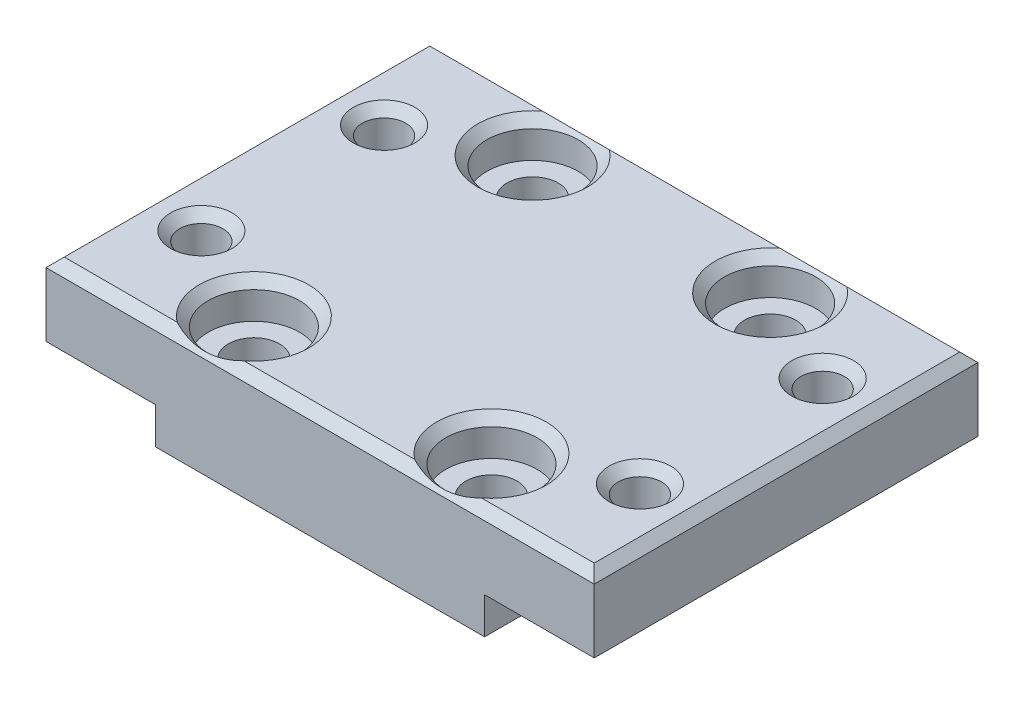
SolidWorks part; units mm, degrees
ref_plane "Plano frontal" through (0, 0, 0) normal (0, 0, 1) x (1, 0, 0)
ref_plane "Plano superior" through (0, 0, 0) normal (0, 1, 0) x (1, 0, 0)
ref_plane "Plano direito" through (0, 0, 0) normal (1, 0, 0) x (0, 0, -1)
sketch "Esboço1" plane through (0, 0, 0) normal (0, 1, 0) x (1, 0, 0)
  line L1 (-30, -21) -> (30, -21)
  line L2 (-30, -21) -> (-30, 21)
  line L3 (-30, 21) -> (30, 21)
  line L4 (30, -21) -> (30, 21)
  line L5 (-30, -21) -> (30, 21) construction
  line L6 (-30, 21) -> (30, -21) construction
  line L7 (-18, -21) -> (18, -21)
  line L8 (-18, -21) -> (-18, 21)
  line L9 (-18, 21) -> (18, 21)
  line L10 (18, -21) -> (18, 21)
  line L11 (-18, -21) -> (18, 21) construction
  line L12 (-18, 21) -> (18, -21) construction
  circle A0 centre (-13, 15.25) radius 2.8
  circle A1 centre (-13, -15.25) radius 2.8
  circle A2 centre (13, 15.25) radius 2.8
  circle A3 centre (13, -15.25) radius 2.8
  circle A4 centre (-24, 10) radius 2.375
  circle A5 centre (-24, -10) radius 2.375
  circle A6 centre (24, -10) radius 2.375
  circle A7 centre (24, 10) radius 2.375
  circle A8 centre (-13, 15.25) radius 5
  circle A9 centre (13, 15.25) radius 5
  circle A10 centre (13, -15.25) radius 5
  circle A11 centre (-13, -15.25) radius 5
  point P0 (0, 0)
  point P20 (0, 0)
  dimension "D3" = 5.6
  dimension "D4" = 5.6
  dimension "D5" = 5.6
  dimension "D6" = 5.6
  dimension "D12" = 4.75
  dimension "D13" = 4.75
  dimension "D14" = 4.75
  dimension "D15" = 4.75
  dimension "D19" = 10
  dimension "D20" = 10
  dimension "D21" = 10
  dimension "D22" = 10
  dimension "D1" = 42
  dimension "D2" = 60
  dimension "D7" = 36
  dimension "D8" = 30.5
  dimension "D9" = 15.25
  dimension "D10" = 26
  dimension "D11" = 13
  dimension "D16" = 6
  dimension "D17" = 20
  dimension "D18" = 6
  dimension "D23" = 11
extrude "Ressalto-extrusão1" add sketch "Esboço1" along normal blind 8 contours L1 L10 L3 L8 A3 A2 A1 A0 | L1 L8 L3 L2 | L10 L1 L4 L3 | A8 A0 | A9 A2 | A10 A3 | A11 A1 region at (-24, 0, 0) region at (8.1414, 0, 15.25) region at (8.1414, 0, -15.25) region at (-13, 0, -20.1086) region at (-13, 0, 10.3914) region at (0, 0, 0) region at (24, 0, 0)
extrude "Corte-extrusão1" cut sketch "Esboço1<3>" against normal blind 4 from vertex contours A8 | A9 | A11 | A10 starting at point (-30, 8, -21)
sketch "Esboço1<3>" plane through (0, 0, 0) normal (0, 1, 0) x (1, 0, 0) same geometry as "Esboço1"
extrude "Ressalto-extrusão4" add sketch "Esboço1<5>" against normal blind 4 contours L1 L10 L3 L8 A11 A10 A9 A8 | A11 A1 | A10 A3 | A9 A2 | A8 A0 region at (8.1414, 0, 15.25) region at (8.1414, 0, -15.25) region at (-13, 0, -20.1086) region at (-13, 0, 10.3914) region at (0, 0, 0)
sketch "Esboço1<5>" plane through (0, 0, 0) normal (0, 1, 0) x (1, 0, 0) same geometry as "Esboço1"
chamfer "Chanfro1" distance 1 angle 45 12 edges at (-30, 8, 0) (24, 8, 12.375) (24, 8, -7.625) (-24, 8, -7.625) (-24, 8, 12.375) (0, 8, -21) (30, 8, 0) (0, 8, 21) (-13, 8, -10.25) (13, 8, 20.25) (-13, 8, 20.25) (13, 8, -10.25)
equation "\"D4@Esboço1\"=\"D3@Esboço1\""
equation "\"D5@Esboço1\"=\"D3@Esboço1\""
equation "\"D6@Esboço1\"=\"D3@Esboço1\""
equation "\"D9@Esboço1\"=\"D8@Esboço1\"/2"
equation "\"D11@Esboço1\"=\"D10@Esboço1\"/2"
equation "\"D13@Esboço1\"=\"D12@Esboço1\""
equation "\"D14@Esboço1\"=\"D12@Esboço1\""
equation "\"D15@Esboço1\"=\"D12@Esboço1\""
equation "\"D20@Esboço1\"=\"D19@Esboço1\""
equation "\"D21@Esboço1\"=\"D19@Esboço1\""
equation "\"D22@Esboço1\"=\"D19@Esboço1\""
equation "\"D18@Esboço1\"=\"D16@Esboço1\""
